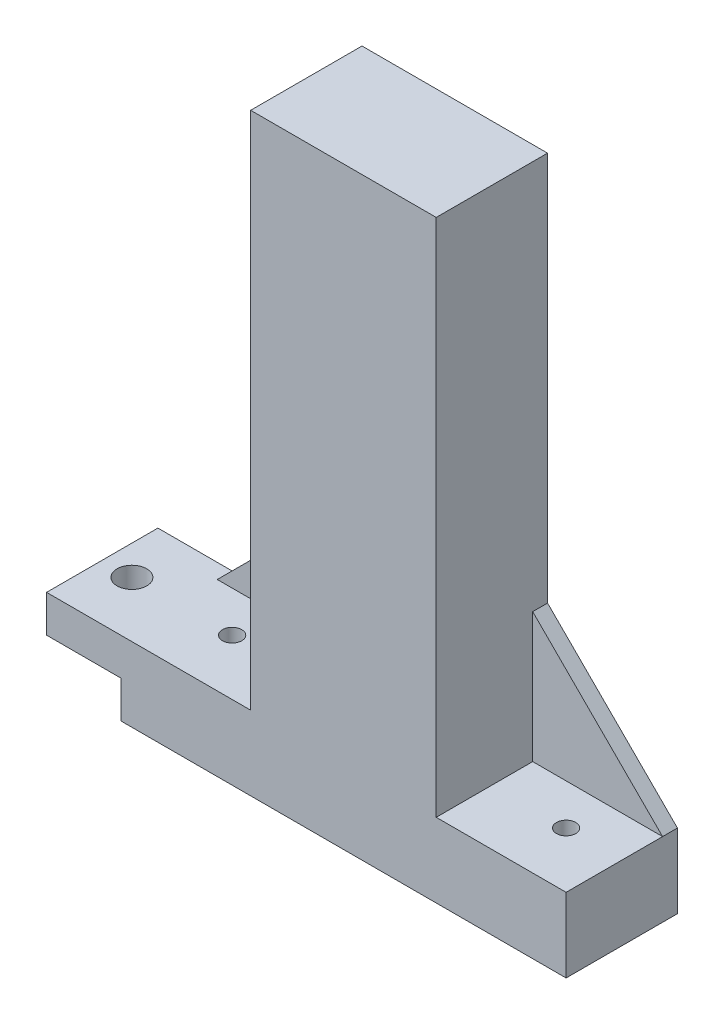
SolidWorks part; units mm, degrees
ref_plane "前基準面" through (0, 0, 0) normal (0, 0, 1) x (1, 0, 0)
ref_plane "上基準面" through (0, 0, 0) normal (0, 1, 0) x (1, 0, 0)
ref_plane "右基準面" through (0, 0, 0) normal (1, 0, 0) x (0, 0, -1)
sketch "草圖2" plane through (0, 0, 0) normal (0, 1, 0) x (1, 0, 0)
  line L5 (-30, 7.5) -> (30, 7.5)
  line L6 (-30, 7.5) -> (-30, -7.5)
  line L7 (-30, -7.5) -> (30, -7.5)
  line L8 (30, 7.5) -> (30, -7.5)
  line L9 (0, -7.5) -> (0, 7.5) construction
  line L10 (-30, 0) -> (30, 0) construction
  circle A4 centre (-22.5, 0) radius 1.3
  circle A5 centre (22.5, 0) radius 1.3
  point P0 (0, 0)
  dimension "D3" = 45
  dimension "D2" = 2.6
  dimension "D1" = 60
  dimension "D4" = 15
extrude "填料-伸長1" add sketch "草圖2" along normal blind 10
sketch "草圖3" plane through (0, 10, 0) normal (0, 1, 0) x (1, 0, 0)
  line L0 (-30, -7.5) -> (30, -7.5) construction
  line L1 (-12.5, 7.5) -> (12.5, 7.5)
  line L2 (-12.5, 7.5) -> (-12.5, -7.5)
  line L3 (-12.5, -7.5) -> (12.5, -7.5)
  line L4 (12.5, 7.5) -> (12.5, -7.5)
  line L5 (0, -7.5) -> (0, 7.5) construction
  line L6 (-12.5, 0) -> (12.5, 0) construction
  point P0 (0, 0)
  point P6 (-22.5, 0)
  point P7 (22.5, 0)
  dimension "D1" = 25
  dimension "D2" = 10
extrude "填料-伸長2" add sketch "草圖3" along normal blind 70
sketch "草圖5" plane through (0, 0, -7.5) normal (0, 0, -1) x (-1, 0, 0)
  line L0 (-30, 10) -> (-12.5, 27.5)
  line L1 (-12.5, 80) -> (-12.5, 10) construction
  line L2 (-12.5, 27.5) -> (-12.5, 10)
  line L3 (-12.5, 10) -> (-30, 10)
  line L4 (0, 0) -> (0, 43.0538) construction
  line L5 (-30, 0) -> (30, 0) construction
  line L6 (12.5, 27.5) -> (12.5, 10)
  line L7 (30, 10) -> (12.5, 27.5)
  line L8 (12.5, 10) -> (30, 10)
  dimension "D1" = 45
extrude "填料-伸長3" add sketch "草圖5" against normal blind 2
sketch "草圖6" plane through (0, 0, 7.5) normal (0, 0, 1) x (1, 0, 0)
  line L0 (-30, 5) -> (-40, 5)
  line L2 (-30, 10) -> (-30, 5)
  line L3 (-30, 10) -> (-40, 10)
  line L4 (-40, 10) -> (-40, 5)
  point P0 (-30, 10)
  dimension "D1" = 10
  dimension "D2" = 5
extrude "填料-伸長4" add sketch "草圖6" against normal up to surface (15 mm away) up to face at (0, 29.375, -7.5)
sketch "草圖7" plane through (0, 10, 0) normal (0, 1, 0) x (1, 0, 0)
  line L3 (-40, 7.5) -> (-40, -7.5) construction
  circle A0 centre (-36, 0) radius 2
  point P2 (-33.1078, 0)
  point P3 (0, 0)
  point P8 (0, 0)
  point P9 (-35.844, 0)
  dimension "D1" = 4
  dimension "D2" = 4
extrude "除料-伸長1" cut sketch "草圖7" against normal through all
